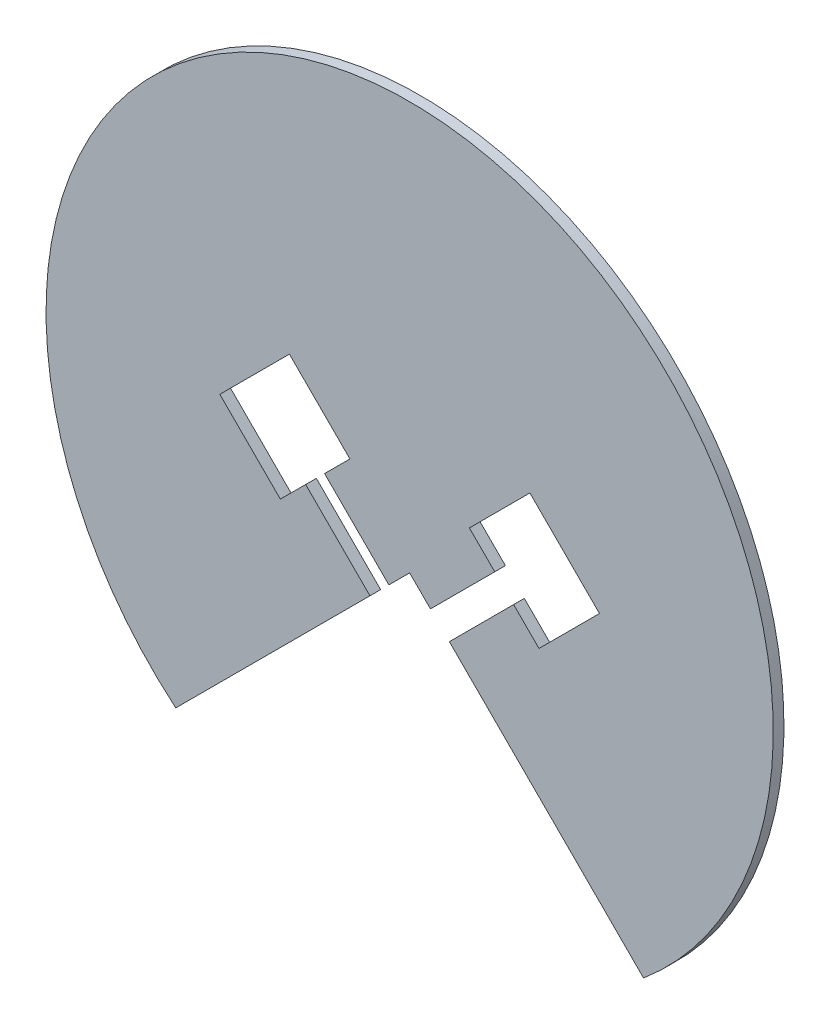
SolidWorks part; units mm, degrees
ref_plane "Front Plane" through (0, 0, 0) normal (0, 0, 1) x (1, 0, 0)
ref_plane "Top Plane" through (0, 0, 0) normal (0, 1, 0) x (1, 0, 0)
ref_plane "Right Plane" through (0, 0, 0) normal (1, 0, 0) x (0, 0, -1)
sketch "Sketch1" plane through (0, 0, 0) normal (0, 0, 1) x (1, 0, 0)
  circle A0 centre (0, 0) radius 215.9
  arc A1 (209.8384, 50.8) -> (-209.8384, 50.8) centre (0, 0) ccw construction
extrude "Boss-Extrude1" add sketch "Sketch1" along normal blind 6.35 contours A0
sketch "Sketch2" plane through (0, 0, 0) normal (0, 0, -1) x (-1, 0, 0)
  line L0 (0, -26.4411) -> (138.8703, -165.3114)
  line L2 (0, -26.4411) -> (-138.8703, -165.3114)
  line L3 (-139.4438, -165.8849) -> (0, -26.4411) construction
  line L4 (0, 0) -> (0, -240.5018) construction
  arc A4 (-138.8703, -165.3114) -> (138.8703, -165.3114) centre (0, 0) ccw
  circle A5 centre (0, 0) radius 215.9 construction
  dimension "D1" = 90
extrude "Cut-Extrude1" cut sketch "Sketch2" against normal through all
sketch "Sketch3" plane through (0, 0, 6.35) normal (0, 0, 1) x (1, 0, 0)
  line L0 (71.393, 50.3401) -> (112.7022, 9.0309)
  line L1 (71.393, 50.3401) -> (35.472, 14.4191)
  line L2 (112.7022, 9.0309) -> (76.7812, -26.8901)
  line L3 (35.472, 14.4191) -> (76.7812, -26.8901)
  line L4 (76.7812, -26.8901) -> (72.2911, -22.4) construction
  line L5 (97.2507, 34.8885) -> (46.1575, -16.2046) construction
  line L6 (50.5139, -0.6229) -> (61.7393, -11.8482)
  line L7 (50.5139, -0.6229) -> (12.3479, -38.7889)
  line L8 (61.7393, -11.8482) -> (23.5732, -50.0143)
  line L9 (12.3479, -38.7889) -> (23.5732, -50.0143)
  line L10 (88.68, 15.0926) -> (77.4547, 26.3179) construction
  line L11 (0, -26.4411) -> (138.8703, -165.3114) construction
  line M8 (0, -26.4411) -> (138.8703, -165.3114)
extrude "Cut-Extrude2" cut sketch "Sketch3" against normal through all contours L8 L6 L3 L7 M8 | L0 L5 L6 L3 L2 | L5 L0 L1 L3 region at (63.7598, 22.0523, 6.35) region at (84.4144, 1.3977, 6.35) region at (37.0436, -25.3186, 6.35)
mirror "Mirror1" about plane through (0, 0, 0) normal (1, 0, 0) of "Cut-Extrude2"
